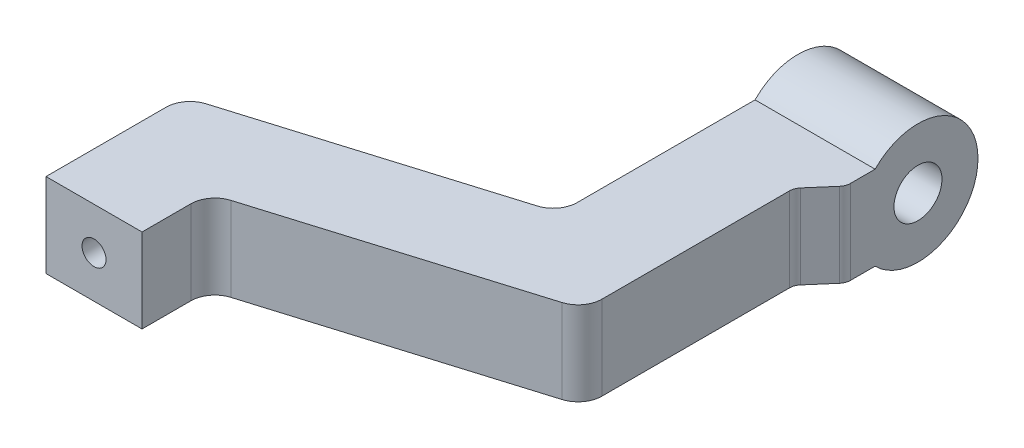
SolidWorks part; units mm, degrees
material "6061 Alloy"
ref_plane "Front Plane" through (0, 0, 0) normal (0, 0, 1) x (1, 0, 0)
ref_plane "Top Plane" through (0, 0, 0) normal (0, 1, 0) x (1, 0, 0)
ref_plane "Right Plane" through (0, 0, 0) normal (1, 0, 0) x (0, 0, -1)
sketch "Sketch2" plane through (0, 0, 0) normal (0, 1, 0) x (1, 0, 0)
  line L0 (-1.5007, 12.1284) -> (2.4993, 12.1284)
  line L1 (15.4993, 31.4445) -> (15.4993, 28.4445)
  line L3 (-1.5007, 12.1284) -> (2.4993, 12.1284)
  line L4 (-1.5007, 12.1284) -> (-1.5007, 17.1284)
  line L6 (2.4993, 12.1284) -> (2.4993, 14.1622)
  line L8 (3.2089, 15.1191) -> (13.7898, 18.3304)
  line L9 (14.4993, 19.2873) -> (14.4993, 27.2873)
  line L10 (-0.7911, 18.0853) -> (9.7898, 21.2966)
  line L11 (10.4993, 22.2535) -> (10.4993, 26.2101)
  line L13 (10.4993, 31.4445) -> (15.4993, 31.4445)
  line L15 (10.4993, 26.2101) -> (10.4993, 31.4445)
  line L16 (15.4993, 28.4445) -> (14.4993, 27.2873)
  line L18 (15.4993, 31.4445) -> (15.4993, 28.8783)
  arc A0 (3.2089, 15.1191) -> (2.4993, 14.1622) centre (3.4993, 14.1622) ccw
  arc A1 (-1.5007, 17.1284) -> (-0.7911, 18.0853) centre (-0.5007, 17.1284) cw
  arc A2 (13.7898, 18.3304) -> (14.4993, 19.2873) centre (13.4993, 19.2873) ccw
  arc A3 (9.7898, 21.2966) -> (10.4993, 22.2535) centre (9.4993, 22.2535) ccw
  point P3 (0.4993, 12.1284)
  point P10 (0, 0)
  point P17 (7.6961, 22.7887)
  dimension "D2" = 1
  dimension "D1" = 4
  dimension "D3" = 15
  dimension "D4" = 4
  dimension "D5" = 4
  dimension "D7" = 8
  dimension "D8" = 5
  dimension "D9" = 3
extrude "Boss-Extrude2" add sketch "Sketch2" along normal blind 3.5 contours A3 L10 A1 L4 L0 L6 A0 L8 A2 L9 L13 L11 region at (-1.2433, 0, -14.6284)
sketch "Sketch3" plane through (10.4993, 0, 0) normal (-1, 0, 0) x (0, 0, 1)
  line L2 (-31.4445, 0) -> (-31.4445, 3.5) construction
  circle A3 centre (-31.4445, 1.75) radius 2.5
extrude "Boss-Extrude3" add sketch "Sketch3" against normal blind 5
fillet "Fillet2" radius 0.5 2 edges at (14.4993, 1.75, -27.2873) (15.4993, 1.75, -28.4445)
sketch "Sketch5" plane through (0, 0, -12.1284) normal (0, 0, 1) x (1, 0, 0)
  line L0 (-1.5007, 3.5) -> (2.4993, 3.5) construction
  line L1 (-1.5007, 0) -> (-1.5007, 3.5) construction
  circle A0 centre (0.4993, 1.75) radius 0.5
  dimension "D1" = 1.75
  dimension "D2" = 2
extrude "Cut-Extrude1" cut sketch "Sketch5" against normal blind 1
sketch "Sketch6" plane through (10.4993, 0, 0) normal (-1, 0, 0) x (0, 0, 1)
  circle A0 centre (-31.4445, 1.75) radius 1
  dimension "D1" = 2
extrude "Cut-Extrude2" cut sketch "Sketch6" against normal through all
